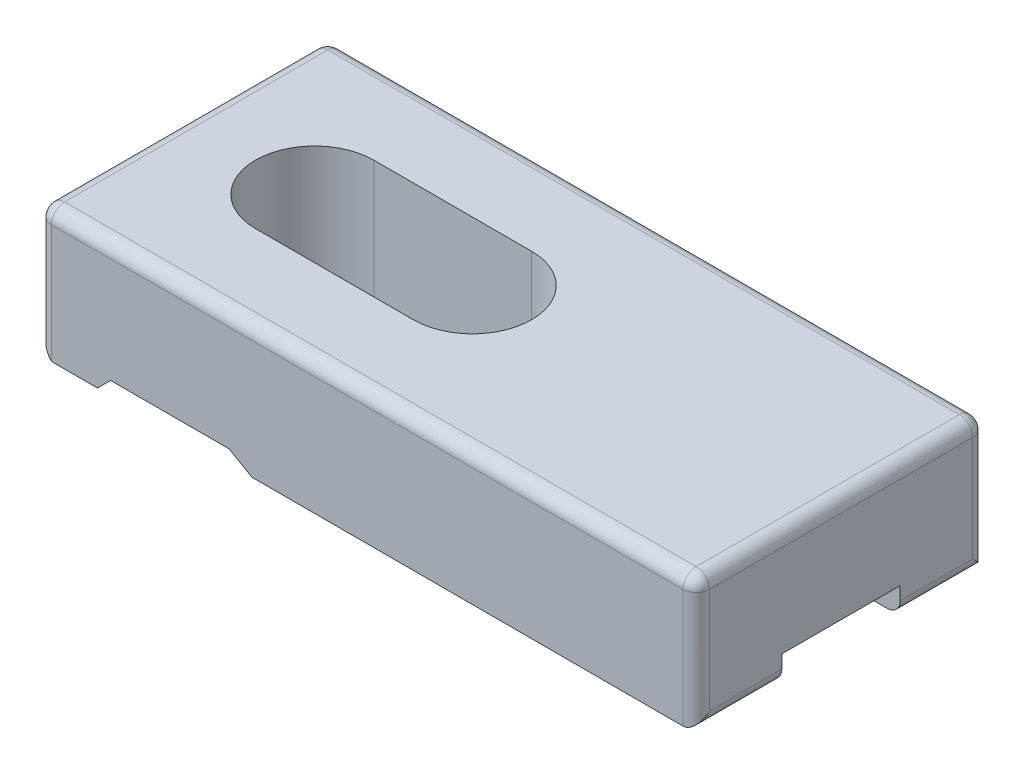
SolidWorks part; units mm, degrees
material "AISI 1045 钢，冷拔"
ref_plane "前视基准面" through (0, 0, 0) normal (0, 0, 1) x (1, 0, 0)
ref_plane "上视基准面" through (0, 0, 0) normal (0, 1, 0) x (1, 0, 0)
ref_plane "右视基准面" through (0, 0, 0) normal (1, 0, 0) x (0, 0, -1)
sketch "草图1" plane through (0, 0, 0) normal (0, 1, 0) x (1, 0, 0)
  line L0 (22, 11) -> (10, 11) construction
  line L1 (0, 0) -> (50, 0)
  line L2 (0, 0) -> (0, 22)
  line L3 (0, 22) -> (50, 22)
  line L4 (50, 0) -> (50, 22)
  line L5 (22, 6.5) -> (10, 6.5)
  line L6 (22, 15.5) -> (10, 15.5)
  arc A0 (22, 6.5) -> (22, 15.5) centre (22, 11) ccw
  arc A1 (10, 15.5) -> (10, 6.5) centre (10, 11) ccw
  point P7 (16, 11)
  dimension "D5" = 4.5
  dimension "D1" = 50
  dimension "D2" = 22
  dimension "D3" = 22
  dimension "D4" = 12
  dimension "D6" = 11
extrude "凸台-拉伸1" add sketch "草图1" along normal blind 10
sketch "草图2" plane through (0, 0, 0) normal (0, -1, 0) x (1, 0, 0)
  line L2 (50, 0) -> (50, -22) construction
  line L3 (50, -6.5) -> (50, -15.5)
  line L4 (50, -15.5) -> (10, -15.5)
  line L13 (10, -6.5) -> (50, -6.5)
  arc A0 (10, -6.5) -> (10, -15.5) centre (10, -11) ccw
extrude "切除-拉伸1" cut sketch "草图2" against normal blind 2
sketch "草图3" plane through (0, 0, 0) normal (0, -1, 0) x (1, 0, 0)
  line L0 (0, -6.5) -> (5.5, -6.5)
  line L1 (0, -22) -> (0, 0) construction
  line L3 (0, -15.5) -> (5.5, -15.5)
  line L4 (5.5, 0) -> (5.5, -6.5)
  line L5 (0, 0) -> (50, 0) construction
  line L6 (50, -22) -> (0, -22) construction
  line L7 (14.5, 0) -> (14.5, -22)
  line L8 (5.5, -15.5) -> (5.5, -22)
  line L9 (5.5, 0) -> (14.5, 0)
  line L10 (5.5, -22) -> (14.5, -22)
  line L11 (0, -6.5) -> (0, -15.5)
  dimension "D1" = 9
  dimension "D2" = 9
  dimension "D3" = 6.5
  dimension "D4" = 5.5
extrude "切除-拉伸2" cut sketch "草图3" against normal blind 1
chamfer "倒角1" distance 1 angle 45 4 edges at (0, 0, -18.75) (5.5, 0, -18.75) (5.5, 0, -3.25) (0, 0, -3.25)
chamfer "倒角2" distance 1 angle 60 2 edges at (14.5, 0, -18.75) (14.5, 0, -3.25) first distance on face at (14.5, 0.5, -18.75) first distance on face at (14.5, 0.5, -3.25)
fillet "圆角1" radius 1 10 edges at (25, 10, -22) (50, 10, -11) (25, 10, 0) (0, 10, -11) (50, 5, 0) (50, 5, -22) (0, 5.5, -22) (0, 5.5, 0) (50, 0, -18.75) (50, 0, -3.25)
